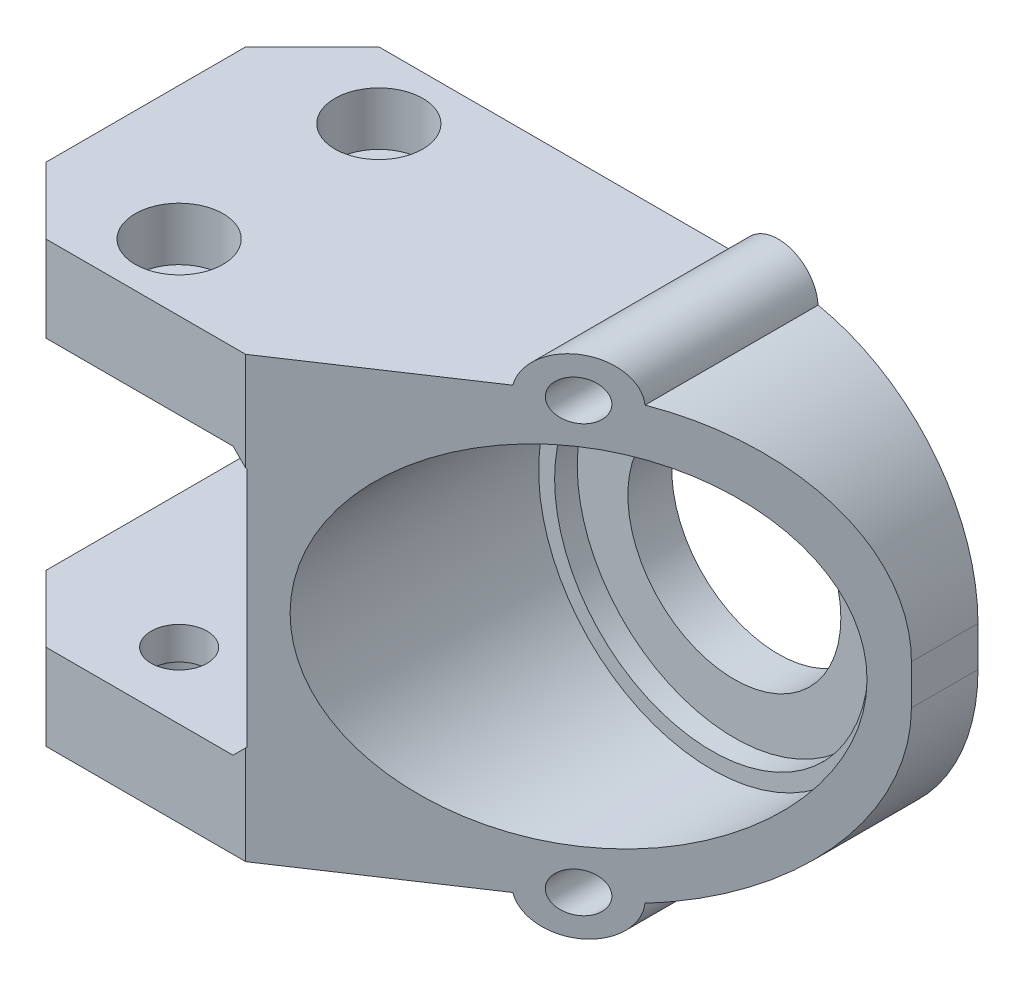
SolidWorks part; units mm, degrees
ref_plane "Front" through (0, 0, 0) normal (0, 0, 1) x (1, 0, 0)
ref_plane "Top" through (0, 0, 0) normal (0, 1, 0) x (1, 0, 0)
ref_plane "Right" through (0, 0, 0) normal (1, 0, 0) x (0, 0, -1)
sketch "Sketch1" plane through (0, 0, 0) normal (0, 1, 0) x (1, 0, 0)
  line L0 (0, 0) -> (0, -50)
  line L1 (0, -50) -> (40, -50)
  line L2 (40, -50) -> (100, -10)
  line L3 (100, -10) -> (100, 0)
  line L4 (100, 0) -> (0, 0)
  line L5 (20, -50) -> (20, 0) construction
  line L6 (70, 0) -> (70, -80.6626) construction
  circle A0 centre (20, -10) radius 4.2
  circle A1 centre (20, -40) radius 4.2
  dimension "D6" = 8.4
  dimension "D7" = 10
  dimension "D8" = 10
  dimension "D1" = 40
  dimension "D2" = 10
  dimension "D3" = 50
  dimension "D4" = 30
  dimension "D5" = 50
extrude "Boss-Extrude1" add sketch "Sketch1" along normal mid plane 66
sketch "Sketch2" plane through (0, 0, 0) normal (0, 0, 1) x (1, 0, 0)
  line L1 (-0.1, 20.1) -> (40.1, 20.1)
  line L2 (-0.1, 20.1) -> (-0.1, -20.1)
  line L3 (-0.1, -20.1) -> (40.1, -20.1)
  line L4 (40.1, 20.1) -> (40.1, -20.1)
  circle A0 centre (70, 0) radius 16
  point P4 (20, -20.1)
  point P6 (-0.1, 0)
  dimension "D2" = 32
  dimension "D1" = 40.2
extrude "Cut-Extrude1" cut sketch "Sketch2" along normal through all
sketch "Sketch3" plane through (0, 0, 0) normal (0, 0, 1) x (1, 0, 0)
  circle A0 centre (70, 0) radius 26
  dimension "D1" = 52
extrude "Cut-Extrude2" cut sketch "Sketch3" along normal through all from vertex starting at point (100, 0, 10)
sketch "Sketch4" plane through (0, 0, 10) normal (0, 0, 1) x (1, 0, 0)
  circle A0 centre (70, 0) radius 23.6
  dimension "D1" = 47.2
extrude "Cut-Extrude3" cut sketch "Sketch4" against normal blind 3.4
fillet "Fillet1" radius 30 2 edges at (100, 33, 5) (100, -33, 5)
chamfer "Chamfer1" distance 2 angle 45 2 edges at (40.1, -20.1, 24.9667) (40.1, 20.1, 24.9667)
sketch "Sketch5" plane through (0, 0, 0) normal (0, 1, 0) x (1, 0, 0)
  circle A0 centre (20, -40) radius 6.6
  circle A1 centre (20, -10) radius 6.6
  dimension "D1" = 13.2
extrude "Cut-Extrude5" cut sketch "Sketch5" against normal through all from offset 25 offset against normal yes
mirror "Mirror1" about plane through (0, 0, 0) normal (0, 1, 0) of "Cut-Extrude5"
chamfer "Chamfer2" distance 10 angle 45 4 edges at (0, -26.55, 0) (0, -26.55, 50) (0, 26.55, 50) (0, 26.55, 0)
sketch "Sketch6" plane through (0, 0, 0) normal (0, 0, 1) x (1, 0, 0)
  line L1 (66.6834, 27) -> (73.3166, 27)
  circle A0 centre (70, 32) radius 3
  circle A1 centre (70, 32) radius 6 construction
  circle A3 centre (70, 0) radius 26 construction
  arc A4 (66.6834, 27) -> (73.3166, 27) centre (70, 32) cw
  dimension "D1" = 6
  dimension "D2" = 12
  dimension "D3" = 5
extrude "Boss-Extrude2" add sketch "Sketch6" along normal up to surface (28 mm away) up to face at (96, 0, 12.6667)
extrude "Cut-Extrude6" cut sketch "Sketch6<2>" along normal through all contours A0
sketch "Sketch6<2>" plane through (0, 0, 0) normal (0, 0, 1) x (1, 0, 0) same geometry as "Sketch6"
mirror "Mirror2" about plane through (0, 0, 0) normal (0, 1, 0) of "Boss-Extrude2", "Cut-Extrude6"
